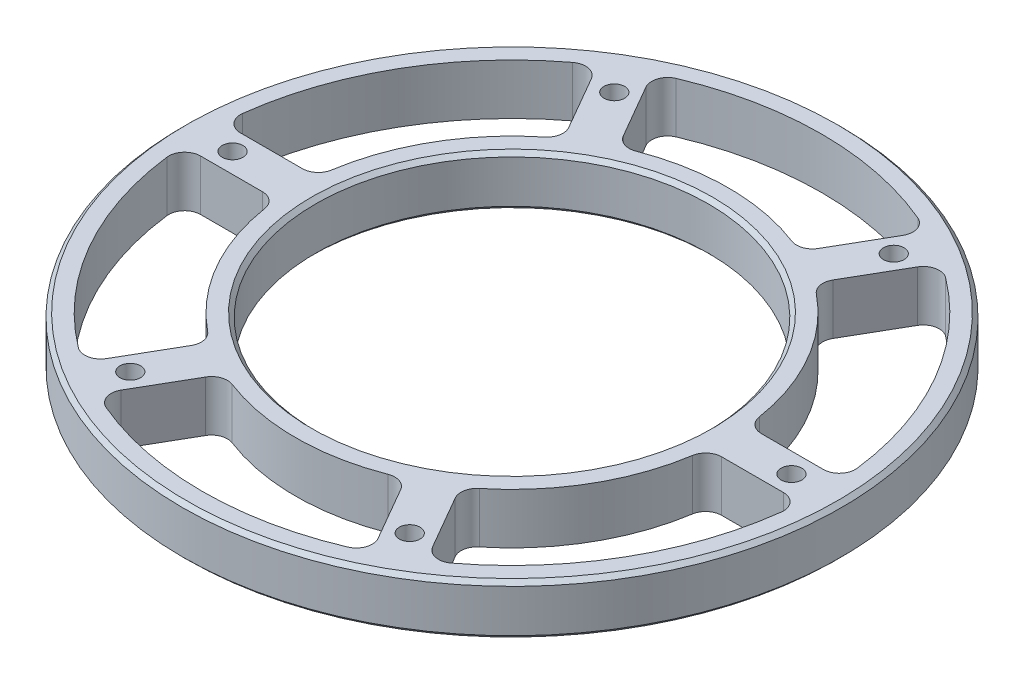
SolidWorks part; units mm, degrees
material "6061-T6 (SS)"
ref_plane "Front Plane" through (0, 0, 0) normal (0, 0, 1) x (1, 0, 0)
ref_plane "Top Plane" through (0, 0, 0) normal (0, 1, 0) x (1, 0, 0)
ref_plane "Right Plane" through (0, 0, 0) normal (1, 0, 0) x (0, 0, -1)
sketch "Sketch2" plane through (0, 0, 0) normal (1, 0, 0) x (0, 0, -1)
  line L0 (-49.2125, 0) -> (-82.55, 0)
  line L1 (-82.55, 0) -> (-82.55, 12.7)
  line L2 (-82.55, 12.7) -> (-49.2125, 12.7)
  line L3 (-49.2125, 12.7) -> (-49.2125, 0)
  dimension "D1" = 82.55
  dimension "D2" = 12.7
  dimension "D4" = 49.2125
ref_axis "Axis1" through (0, -0.5, 0) along (0, 1, 0)
revolve "Revolve1" add sketch "Sketch2" angle 360 about axis through (0, -0.5, 0) along (0, 1, 0)
hole_wizard "#6 (0.204) Diameter Hole1" positions "Sketch6" profile "Sketch7" hole size "#6" standard "ANSI Inch" end condition through all
sketch "Sketch6" plane through (0, 12.7, 0) normal (0, 1, 0) x (1, 0, 0)
  line L0 (0, 0) -> (-69.8201, 120.932) construction
  line L2 (0, 0) -> (0, 109.0908) construction
  point P0 (-35, 60.6218)
  dimension "D1" = 30
  dimension "D2" = 70
sketch "Sketch7" plane through (-35, 12.7, -60.6218) normal (1, 0, 0) x (0, 0, 1)
  line L0 (0, 0) -> (0, 12.7)
  line L1 (0, 12.7) -> (2.5908, 12.7)
  line L2 (2.5908, 12.7) -> (2.5908, 0)
  line L5 (2.5908, 0) -> (0, 0)
  line L11 (0, -6.35) -> (0, 107.95) construction
  dimension "Thru Hole Dia." = 5.1816
  dimension "Thru Hole Depth" = 12.7
pattern_circular "CirPattern3" count 6 over 360 about axis through (0, -0.5, 0) along (0, 1, 0) of "#6 (0.204) Diameter Hole1"
sketch "Sketch8" plane through (0, 12.7, 0) normal (0, 1, 0) x (1, 0, 0)
  line L4 (0, 0) -> (0, 93.9995) construction
  line L5 (-22.6606, 49.2493) -> (-34.3642, 69.5205)
  line L6 (22.6606, 49.2493) -> (34.3642, 69.5205)
  line L7 (0, 0) -> (-35, 60.6218) construction
  arc A0 (-22.6606, 49.2493) -> (22.6606, 49.2493) centre (0, 0) cw
  arc A1 (-34.3642, 69.5205) -> (34.3642, 69.5205) centre (0, 0) cw
  circle A2 centre (0, 0) radius 82.55 construction
  circle A4 centre (0, 0) radius 49.2125 construction
  dimension "D1" = 5
  dimension "D2" = 5
  dimension "D3" = 5
extrude "Cut-Extrude1" cut sketch "Sketch8" against normal through all
fillet "Fillet1" radius 4 4 edges at (-22.6606, 6.35, -49.2493) (22.6606, 6.35, -49.2493) (34.3642, 6.35, -69.5205) (-34.3642, 6.35, -69.5205)
pattern_circular "CirPattern4" count 6 over 360 about axis through (0, -0.5, 0) along (0, 1, 0) of "Cut-Extrude1", "Fillet1"
chamfer "Chamfer1" distance 1 angle 45 2 edges at (0, 12.7, -49.2125) (0, 0, -49.2125)
chamfer "Chamfer2" distance 1 angle 45 2 edges at (0, 12.7, -82.55) (0, 0, -82.55)
equation "\"TubeDiameter\" = 6.500in"
equation "\"D1@Sketch2\"=\"TubeDiameter\"/2"
